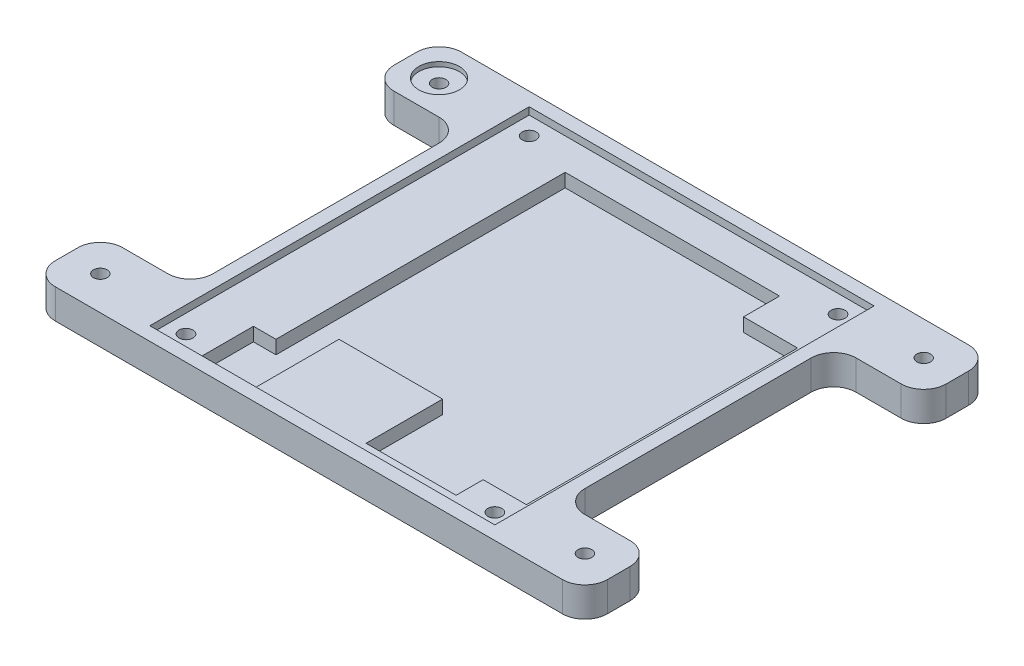
SolidWorks part; units mm, degrees
ref_plane "Front Plane" through (0, 0, 0) normal (0, 0, 1) x (1, 0, 0)
ref_plane "Top Plane" through (0, 0, 0) normal (0, 1, 0) x (1, 0, 0)
ref_plane "Right Plane" through (0, 0, 0) normal (1, 0, 0) x (0, 0, -1)
sketch "Sketch1" plane through (0, 0, 0) normal (0, 1, 0) x (1, 0, 0)
  line L0 (-36.907, 45.3779) -> (-36.907, -14.8421)
  line L1 (-44.307, -29.8421) -> (45.693, -29.8421)
  line L2 (45.693, -14.8421) -> (45.693, 45.3779)
  line L3 (45.693, 60.3779) -> (-44.307, 60.3779)
  line L4 (-44.307, 60.3779) -> (-56.907, 60.3779)
  line L5 (-56.907, 60.3779) -> (-56.907, 45.3779)
  line L6 (-56.907, 45.3779) -> (-36.907, 45.3779)
  line L7 (-44.307, -29.8421) -> (-56.907, -29.8421)
  line L8 (-56.907, -29.8421) -> (-56.907, -14.8421)
  line L9 (-56.907, -14.8421) -> (-36.907, -14.8421)
  line L10 (45.693, -29.8421) -> (65.693, -29.8421)
  line L11 (65.693, -29.8421) -> (65.693, -14.8421)
  line L12 (65.693, -14.8421) -> (45.693, -14.8421)
  line L13 (45.693, 60.3779) -> (65.693, 60.3779)
  line L14 (65.693, 60.3779) -> (65.693, 45.3779)
  line L15 (65.693, 45.3779) -> (45.693, 45.3779)
  dimension "D1" = 90.22
  dimension "D2" = 82.6
  dimension "D3" = 20
  dimension "D4" = 15
  dimension "D5" = 15
  dimension "D6" = 20
  dimension "D7" = 15
  dimension "D8" = 15
  dimension "D10" = 20
  dimension "D11" = 20
extrude "Boss-Extrude1" add sketch "Sketch1" along normal blind 6.6
sketch "Sketch2" plane through (0, 6.6, 0) normal (0, 1, 0) x (1, 0, 0)
  line L0 (-33.907, 57.3779) -> (-33.907, -26.8421)
  line L1 (-33.907, -26.8421) -> (42.693, -26.8421)
  line L2 (42.693, -26.8421) -> (42.693, 57.3779)
  line L3 (42.693, 57.3779) -> (-33.907, 57.3779)
  line L4 (-36.907, 45.3779) -> (-36.907, -14.8421) construction
  line L5 (-56.907, -29.8421) -> (65.693, -29.8421) construction
  line L6 (65.693, 60.3779) -> (-56.907, 60.3779) construction
  line L7 (45.693, -14.8421) -> (45.693, 45.3779) construction
  circle A0 centre (38.683, 53.3679) radius 1.55
  circle A1 centre (-29.897, 53.3679) radius 1.55
  circle A2 centre (-29.897, -22.8321) radius 1.55
  circle A3 centre (38.683, -22.8321) radius 1.55
  dimension "D8" = 76.6
  dimension "D1" = 3
  dimension "D2" = 3
  dimension "D3" = 84.22
  dimension "D4" = 76.2
  dimension "D5" = 4.01
  dimension "D6" = 68.58
  dimension "D7" = 4.01
  dimension "D9" = 3
  dimension "D10" = 3
  dimension "D11" = 4.01
  dimension "D12" = 4.01
  dimension "D13" = 3
extrude "Cut-Extrude9" cut sketch "Sketch2<5>" against normal blind 1.6 contours L3 L0 L1 L2
sketch "Sketch2<5>" plane through (0, 6.6, 0) normal (0, 1, 0) x (1, 0, 0) same geometry as "Sketch2"
sketch "Sketch11" plane through (0, 5, 0) normal (0, 1, 0) x (1, 0, 0)
  line L0 (-18.907, 50.3779) -> (-18.907, -13.8421)
  line L1 (-23.907, -26.8421) -> (-11.907, -26.8421)
  line L2 (-11.907, -6.8421) -> (11.093, -6.8421)
  line L3 (11.093, -6.8421) -> (11.093, -23.8421)
  line L4 (11.093, -23.8421) -> (31.093, -23.8421)
  line L5 (31.093, -23.8421) -> (31.093, -17.8421)
  line L6 (28.693, 50.3779) -> (-18.907, 50.3779)
  line L7 (-18.907, -13.8421) -> (-23.907, -13.8421)
  line L8 (-23.907, -13.8421) -> (-23.907, -26.8421)
  line L9 (-11.907, -6.8421) -> (-11.907, -26.8421)
  line L11 (31.093, -17.8421) -> (40.693, -17.8421)
  line L12 (40.693, -17.8421) -> (40.693, 42.3779)
  line L13 (40.693, 42.3779) -> (28.693, 42.3779)
  line L14 (28.693, 42.3779) -> (28.693, 50.3779)
  line L16 (-33.907, 57.3779) -> (-33.907, -26.8421) construction
  line L17 (-33.907, -26.8421) -> (42.693, -26.8421) construction
  line L18 (42.693, -26.8421) -> (42.693, 57.3779) construction
  line L19 (42.693, 57.3779) -> (-33.907, 57.3779) construction
  line L21 (-33.907, 57.3779) -> (-33.907, -26.8421) construction
  point P23 (28.693, 46.3779)
  point P29 (31.093, -20.8421)
  dimension "D1" = 15
  dimension "D2" = 20
  dimension "D3" = 65
  dimension "D4" = 3
  dimension "D5" = 9
  dimension "D6" = 2
  dimension "D7" = 14
  dimension "D8" = 7
  dimension "D9" = 13
  dimension "D10" = 10
  dimension "D11" = 22
  dimension "D12" = 45
  dimension "D13" = 15
extrude "Cut-Extrude10" cut sketch "Sketch11" against normal blind 3
extrude "Cut-Extrude3" cut sketch "Sketch2" against normal through all contours A1 | A0 | A3 | A2
sketch "Sketch4" plane through (-31.1286, 6.6, 0) normal (0, -1, 0) x (-1, 0, 0)
  line L0 (-19.1435, -1.7378) -> (-23.3424, -3.9435)
  line L1 (-3.6123, -3.9435) -> (-7.8102, -1.7378)
  line L2 (-7.8102, -6.1461) -> (-3.6123, -3.9435)
  line L3 (-23.3424, -3.9435) -> (-19.1435, -6.1461)
  line L4 (-19.1435, -7.1869) -> (-23.3424, -9.3906)
  line L5 (-3.6123, -9.3906) -> (-7.8102, -7.1869)
  line L6 (-7.8102, -11.5952) -> (-3.6123, -9.3906)
  line L7 (-23.3424, -9.3906) -> (-19.1435, -11.5952)
  line L8 (-19.1435, -12.635) -> (-23.3424, -14.8387)
  line L9 (-3.6123, -14.8387) -> (-7.8102, -12.635)
  line L10 (-7.8102, -17.0423) -> (-3.6123, -14.8387)
  line L11 (-23.3424, -14.8387) -> (-19.1435, -17.0423)
  line L12 (-7.5017, 11.7391) -> (-4.8823, 11.7391)
  line L13 (-10.0888, 5.39) -> (-10.0888, 7.6364)
  line L14 (-4.8823, 1.2873) -> (-7.5017, 1.2873)
  line L15 (-4.663, 11.5198) -> (-4.663, 1.5066)
  line L16 (-6.3249, 2.5097) -> (-6.3249, 10.5177)
  line L17 (-7.2487, 2.5097) -> (-6.3249, 2.5097)
  line L18 (-8.4041, 7.7514) -> (-8.4041, 5.2749)
  line L19 (-6.3249, 10.5177) -> (-7.2487, 10.5177)
  line L20 (-22.2342, 4.125) -> (-22.2342, 11.5198)
  line L21 (-16.8287, 11.5198) -> (-16.8287, 4.125)
  line L22 (-18.2714, 11.7391) -> (-17.048, 11.7391)
  line L23 (-18.4916, 4.127) -> (-18.4916, 11.5198)
  line L24 (-20.5713, 11.5198) -> (-20.5713, 4.127)
  line L25 (-22.0149, 11.7391) -> (-20.7905, 11.7391)
  line L26 (-14.3304, 10.4184) -> (-14.3304, 1.5066)
  line L27 (-15.903, 10.4184) -> (-14.3304, 10.4184)
  line L28 (-16.1228, 11.5198) -> (-16.1228, 10.6377)
  line L29 (-10.9808, 11.7391) -> (-15.903, 11.7391)
  line L30 (-10.7605, 10.6377) -> (-10.7605, 11.5198)
  line L31 (-12.5529, 10.4184) -> (-10.9808, 10.4184)
  line L32 (-12.5529, 1.5066) -> (-12.5529, 10.4184)
  line L33 (-14.1121, 1.2873) -> (-12.7722, 1.2873)
  spline S0 degree 3 poles (-7.8102, -1.7378) (-13.2484, -3.8532) (-13.7073, -3.8532) (-19.1435, -1.7378) knots 4 4 4 4 5 5 5 5
  spline S1 degree 3 poles (-19.1435, -6.1461) (-13.7073, -4.0318) (-13.2484, -4.0318) (-7.8102, -6.1461) knots 1 1 1 1 2 2 2 2
  spline S2 degree 3 poles (-7.8102, -7.1869) (-13.2484, -9.3013) (-13.7073, -9.3013) (-19.1435, -7.1869) knots 4 4 4 4 5 5 5 5
  spline S3 degree 3 poles (-19.1435, -11.5952) (-13.7073, -9.4799) (-13.2484, -9.4799) (-7.8102, -11.5952) knots 1 1 1 1 2 2 2 2
  spline S4 degree 3 poles (-7.8102, -12.635) (-13.2484, -14.7504) (-13.7073, -14.7504) (-19.1435, -12.635) knots 4 4 4 4 5 5 5 5
  spline S5 degree 3 poles (-19.1435, -17.0423) (-13.7073, -14.928) (-13.2484, -14.928) (-7.8102, -17.0423) knots 1 1 1 1 2 2 2 2
  spline S6 degree 3 poles (-9.5158, 11.0207) (-9.1398, 11.5079) (-8.5192, 11.7391) (-7.5017, 11.7391) knots 10 10 10 10 11 11 11 11
  spline S7 degree 3 poles (-10.0888, 7.6364) (-10.0888, 9.2824) (-10.0709, 10.3559) (-9.5158, 11.0207) knots 9 9 9 9 10 10 10 10
  spline S8 degree 3 poles (-9.5158, 2.0057) (-10.0709, 2.6705) (-10.0888, 3.744) (-10.0888, 5.39) knots 7 7 7 7 8 8 8 8
  spline S9 degree 3 poles (-7.5017, 1.2873) (-8.5192, 1.2873) (-9.1398, 1.5185) (-9.5158, 2.0057) knots 6 6 6 6 7 7 7 7
  spline S10 degree 3 poles (-4.7206, 1.3459) (-4.7558, 1.3112) (-4.8039, 1.2873) (-4.8823, 1.2873) knots 4 4 4 4 5 5 5 5
  spline S11 degree 3 poles (-4.663, 1.5066) (-4.663, 1.4282) (-4.6858, 1.3806) (-4.7206, 1.3459) knots 3 3 3 3 4 4 4 4
  spline S12 degree 3 poles (-4.7206, 11.6815) (-4.6858, 11.6458) (-4.663, 11.5992) (-4.663, 11.5198) knots 1 1 1 1 2 2 2 2
  spline S13 degree 3 poles (-4.8823, 11.7391) (-4.8039, 11.7391) (-4.7558, 11.7152) (-4.7206, 11.6815) knots 0 0 0 0 1 1 1 1
  spline S14 degree 3 poles (-8.0885, 2.8014) (-7.9, 2.5752) (-7.6565, 2.5097) (-7.2487, 2.5097) knots 5 5 5 5 6 6 6 6
  spline S15 degree 3 poles (-8.4041, 5.2749) (-8.4041, 3.8551) (-8.3793, 3.1507) (-8.0885, 2.8014) knots 4 4 4 4 5 5 5 5
  spline S16 degree 3 poles (-8.0885, 10.225) (-8.3793, 9.8757) (-8.4041, 9.1713) (-8.4041, 7.7514) knots 2 2 2 2 3 3 3 3
  spline S17 degree 3 poles (-7.2487, 10.5177) (-7.6565, 10.5177) (-7.9, 10.4512) (-8.0885, 10.225) knots 1 1 1 1 2 2 2 2
  spline S18 degree 3 poles (-21.6364, 1.9045) (-22.1156, 2.4611) (-22.2342, 3.1259) (-22.2342, 4.125) knots 20 20 20 20 21 21 21 21
  spline S19 degree 3 poles (-19.5364, 1.1554) (-20.5658, 1.1554) (-21.2286, 1.4312) (-21.6364, 1.9045) knots 19 19 19 19 20 20 20 20
  spline S20 degree 3 poles (-17.4027, 1.9035) (-17.8467, 1.4143) (-18.5189, 1.1554) (-19.5364, 1.1554) knots 18 18 18 18 19 19 19 19
  spline S21 degree 3 poles (-16.8287, 4.125) (-16.8287, 3.0485) (-16.9751, 2.3738) (-17.4027, 1.9035) knots 17 17 17 17 18 18 18 18
  spline S22 degree 3 poles (-16.8873, 11.6815) (-16.8515, 11.6458) (-16.8287, 11.5992) (-16.8287, 11.5198) knots 15 15 15 15 16 16 16 16
  spline S23 degree 3 poles (-17.048, 11.7391) (-16.9691, 11.7391) (-16.921, 11.7152) (-16.8873, 11.6815) knots 14 14 14 14 15 15 15 15
  spline S24 degree 3 poles (-18.4321, 11.6815) (-18.3984, 11.7152) (-18.3502, 11.7391) (-18.2714, 11.7391) knots 12 12 12 12 13 13 13 13
  spline S25 degree 3 poles (-18.4916, 11.5198) (-18.4916, 11.5992) (-18.4673, 11.6458) (-18.4321, 11.6815) knots 11 11 11 11 12 12 12 12
  spline S26 degree 3 poles (-18.8007, 2.6238) (-18.5636, 2.8848) (-18.4916, 3.3283) (-18.4916, 4.127) knots 9 9 9 9 10 10 10 10
  spline S27 degree 3 poles (-19.5151, 2.344) (-19.2085, 2.344) (-18.9773, 2.4294) (-18.8007, 2.6238) knots 8 8 8 8 9 9 9 9
  spline S28 degree 3 poles (-20.2627, 2.6218) (-20.0925, 2.4353) (-19.8514, 2.344) (-19.5151, 2.344) knots 7 7 7 7 8 8 8 8
  spline S29 degree 3 poles (-20.5713, 4.127) (-20.5713, 3.3561) (-20.5127, 2.8977) (-20.2627, 2.6218) knots 6 6 6 6 7 7 7 7
  spline S30 degree 3 poles (-20.6298, 11.6815) (-20.5946, 11.6458) (-20.5713, 11.5992) (-20.5713, 11.5198) knots 4 4 4 4 5 5 5 5
  spline S31 degree 3 poles (-20.7905, 11.7391) (-20.7122, 11.7391) (-20.6645, 11.7152) (-20.6298, 11.6815) knots 3 3 3 3 4 4 4 4
  spline S32 degree 3 poles (-22.1756, 11.6815) (-22.1414, 11.7152) (-22.0928, 11.7391) (-22.0149, 11.7391) knots 1 1 1 1 2 2 2 2
  spline S33 degree 3 poles (-22.2342, 11.5198) (-22.2342, 11.5992) (-22.2104, 11.6458) (-22.1756, 11.6815) knots 0 0 0 0 1 1 1 1
  spline S34 degree 3 poles (-16.0652, 10.476) (-16.03, 10.4413) (-15.9819, 10.4184) (-15.903, 10.4184) knots 17 17 17 17 18 18 18 18
  spline S35 degree 3 poles (-16.1228, 10.6377) (-16.1228, 10.5593) (-16.0985, 10.5107) (-16.0652, 10.476) knots 16 16 16 16 17 17 17 17
  spline S36 degree 3 poles (-16.0652, 11.6815) (-16.0985, 11.6458) (-16.1228, 11.5992) (-16.1228, 11.5198) knots 14 14 14 14 15 15 15 15
  spline S37 degree 3 poles (-15.903, 11.7391) (-15.9819, 11.7391) (-16.03, 11.7152) (-16.0652, 11.6815) knots 13 13 13 13 14 14 14 14
  spline S38 degree 3 poles (-10.819, 11.6815) (-10.8548, 11.7152) (-10.9019, 11.7391) (-10.9808, 11.7391) knots 11 11 11 11 12 12 12 12
  spline S39 degree 3 poles (-10.7605, 11.5198) (-10.7605, 11.5992) (-10.7843, 11.6458) (-10.819, 11.6815) knots 10 10 10 10 11 11 11 11
  spline S40 degree 3 poles (-10.819, 10.476) (-10.7843, 10.5107) (-10.7605, 10.5593) (-10.7605, 10.6377) knots 8 8 8 8 9 9 9 9
  spline S41 degree 3 poles (-10.9808, 10.4184) (-10.9019, 10.4184) (-10.8548, 10.4413) (-10.819, 10.476) knots 7 7 7 7 8 8 8 8
  spline S42 degree 3 poles (-12.6114, 1.3459) (-12.5757, 1.3806) (-12.5529, 1.4282) (-12.5529, 1.5066) knots 4 4 4 4 5 5 5 5
  spline S43 degree 3 poles (-12.7722, 1.2873) (-12.6943, 1.2873) (-12.6457, 1.3112) (-12.6114, 1.3459) knots 3 3 3 3 4 4 4 4
  spline S44 degree 3 poles (-14.2729, 1.3459) (-14.2376, 1.3112) (-14.19, 1.2873) (-14.1121, 1.2873) knots 1 1 1 1 2 2 2 2
  spline S45 degree 3 poles (-14.3304, 1.5066) (-14.3304, 1.4282) (-14.3076, 1.3806) (-14.2729, 1.3459) knots 0 0 0 0 1 1 1 1
extrude "Boss-Extrude2" [suppressed] add sketch "Sketch4" against normal blind 1.6
fillet "Fillet1" radius 5 12 edges at (-56.907, 3.3, -45.3779) (-56.907, 3.3, -60.3779) (-56.907, 3.3, 29.8421) (65.693, 3.3, -60.3779) (45.693, 3.3, -45.3779) (65.693, 3.3, -45.3779) (65.693, 3.3, 29.8421) (-56.907, 3.3, 14.8421) (65.693, 3.3, 14.8421) (45.693, 3.3, 14.8421) (-36.907, 3.3, 14.8421) (-36.907, 3.3, -45.3779)
sketch "Sketch5" plane through (0, 6.6, 0) normal (0, 1, 0) x (1, 0, 0)
  line L0 (60.693, 60.3779) -> (-51.907, 60.3779) construction
  line L1 (-56.907, 55.3779) -> (-56.907, 50.3779) construction
  line L2 (-41.907, -14.8421) -> (-51.907, -14.8421) construction
  line L3 (-56.907, -19.8421) -> (-56.907, -24.8421) construction
  line L4 (60.693, -14.8421) -> (50.693, -14.8421) construction
  line L5 (65.693, -24.8421) -> (65.693, -19.8421) construction
  line L6 (65.693, 50.3779) -> (65.693, 55.3779) construction
  circle A0 centre (-49.407, 52.8779) radius 1.525
  circle A1 centre (-49.407, 52.8779) radius 4.5
  circle A2 centre (-49.407, -22.3421) radius 1.525
  circle A3 centre (58.193, -22.3421) radius 1.525
  circle A4 centre (58.193, 52.8779) radius 1.525
  dimension "D1" = 3.05
  dimension "D4" = 9
  dimension "D7" = 3.05
  dimension "D10" = 3.05
  dimension "D13" = 3.05
  dimension "D2" = 7.5
  dimension "D3" = 7.5
  dimension "D5" = 7.5
  dimension "D6" = 7.5
  dimension "D8" = 7.5
  dimension "D9" = 7.5
  dimension "D11" = 7.5
  dimension "D12" = 7.5
extrude "Cut-Extrude4" cut sketch "Sketch5" against normal blind 10 contours A0 | A2 | A3 | A4
extrude "Cut-Extrude5" cut sketch "Sketch5<3>" against normal blind 1 contours A1
sketch "Sketch5<3>" plane through (0, 6.6, 0) normal (0, 1, 0) x (1, 0, 0) same geometry as "Sketch5"
sketch "Sketch6" plane through (0, 0, 0) normal (0, -1, 0) x (1, 0, 0)
  line L1 (-52.6108, 22.3968) -> (-51.0563, 19.5949)
  line L2 (-51.0563, 19.5949) -> (-47.8525, 19.5402)
  line L3 (-47.8525, 19.5402) -> (-46.2032, 22.2874)
  line L4 (-46.2032, 22.2874) -> (-47.7577, 25.0894)
  line L5 (-47.7577, 25.0894) -> (-50.9616, 25.1441)
  line L6 (-50.9616, 25.1441) -> (-52.6108, 22.3968)
  line L7 (58.333, 25.5433) -> (55.4907, 24.064)
  line L8 (55.4907, 24.064) -> (55.3506, 20.8628)
  line L9 (55.3506, 20.8628) -> (58.0529, 19.1409)
  line L10 (58.0529, 19.1409) -> (60.8953, 20.6202)
  line L11 (60.8953, 20.6202) -> (61.0354, 23.8215)
  line L12 (61.0354, 23.8215) -> (58.333, 25.5433)
  line L13 (60.5667, -50.7254) -> (57.5157, -49.746)
  line L14 (57.5157, -49.746) -> (55.142, -51.8984)
  line L15 (55.142, -51.8984) -> (55.8193, -55.0304)
  line L16 (55.8193, -55.0304) -> (58.8702, -56.0098)
  line L17 (58.8702, -56.0098) -> (61.2439, -53.8573)
  line L18 (61.2439, -53.8573) -> (60.5667, -50.7254)
  line L19 (-52.6111, -52.8458) -> (-51.0369, -55.6367)
  line L20 (-51.0369, -55.6367) -> (-47.8327, -55.6688)
  line L21 (-47.8327, -55.6688) -> (-46.2029, -52.91)
  line L22 (-46.2029, -52.91) -> (-47.7772, -50.1191)
  line L23 (-47.7772, -50.1191) -> (-50.9813, -50.087)
  line L24 (-50.9813, -50.087) -> (-52.6111, -52.8458)
  line L25 (-26.9565, 21.559) -> (-27.3242, 24.7422)
  line L26 (-27.3242, 24.7422) -> (-30.2648, 26.0152)
  line L27 (-30.2648, 26.0152) -> (-32.8376, 24.1052)
  line L28 (-32.8376, 24.1052) -> (-32.4698, 20.9221)
  line L29 (-32.4698, 20.9221) -> (-29.5293, 19.649)
  line L30 (-29.5293, 19.649) -> (-26.9565, 21.559)
  line L31 (41.3181, 21.009) -> (41.5794, 24.2026)
  line L32 (41.5794, 24.2026) -> (38.9443, 26.0257)
  line L33 (38.9443, 26.0257) -> (36.0479, 24.6552)
  line L34 (36.0479, 24.6552) -> (35.7866, 21.4616)
  line L35 (35.7866, 21.4616) -> (38.4217, 19.6385)
  line L36 (38.4217, 19.6385) -> (41.3181, 21.009)
  line L37 (41.4359, -55.0077) -> (41.4796, -51.8037)
  line L38 (41.4796, -51.8037) -> (38.7267, -50.1639)
  line L39 (38.7267, -50.1639) -> (35.9301, -51.728)
  line L40 (35.9301, -51.728) -> (35.8864, -54.932)
  line L41 (35.8864, -54.932) -> (38.6393, -56.5719)
  line L42 (38.6393, -56.5719) -> (41.4359, -55.0077)
  line L43 (-26.7033, -53.6279) -> (-28.0749, -50.7321)
  line L44 (-28.0749, -50.7321) -> (-31.2687, -50.472)
  line L45 (-31.2687, -50.472) -> (-33.0907, -53.1078)
  line L46 (-33.0907, -53.1078) -> (-31.7191, -56.0037)
  line L47 (-31.7191, -56.0037) -> (-28.5254, -56.2638)
  line L48 (-28.5254, -56.2638) -> (-26.7033, -53.6279)
  circle A0 centre (-49.407, 22.3421) radius 2.775 construction
  circle A1 centre (58.193, 22.3421) radius 2.775 construction
  circle A2 centre (58.193, -52.8779) radius 2.775 construction
  circle A3 centre (-49.407, -52.8779) radius 2.775 construction
  circle A4 centre (58.193, -52.8779) radius 1.525 construction
  circle A5 centre (-29.897, 22.8321) radius 2.775 construction
  circle A6 centre (38.683, 22.8321) radius 2.775 construction
  circle A7 centre (38.683, -53.3679) radius 2.775 construction
  circle A8 centre (-29.897, -53.3679) radius 2.775 construction
  point P40 (-51.7962, -51.4664)
  dimension "D1" = 5.55
  dimension "D2" = 5.55
  dimension "D3" = 5.55
  dimension "D4" = 5.55
  dimension "D5" = 5.55
  dimension "D6" = 5.55
  dimension "D7" = 5.55
  dimension "D8" = 5.55
extrude "Cut-Extrude6" cut sketch "Sketch6" against normal blind 2.4
sketch "Sketch10" plane through (0, 0, 0) normal (0, -1, 0) x (1, 0, 0)
  line L0 (20.693, -35.3779) -> (20.693, -29.8779)
  line L1 (20.693, -29.8779) -> (15.693, -29.8779)
  line L2 (15.693, -29.8779) -> (15.693, -35.3779)
  line L3 (15.693, -35.3779) -> (20.693, -35.3779)
  line L4 (-16.807, 64.8621) -> (-16.807, -60.1379) construction
  line L7 (20.693, -5.6579) -> (20.693, -0.1579)
  line L8 (20.693, -0.1579) -> (15.693, -0.1579)
  line L9 (15.693, -0.1579) -> (15.693, -5.6579)
  line L10 (15.693, -5.6579) -> (20.693, -5.6579)
  line L11 (45.693, 9.8421) -> (45.693, -40.3779) construction
  line L12 (60.693, -60.3779) -> (-51.907, -60.3779) construction
  line L13 (-51.907, 29.8421) -> (60.693, 29.8421) construction
  line L15 (-49.307, -5.6579) -> (-54.307, -5.6579)
  line L16 (-49.307, -0.1579) -> (-49.307, -5.6579)
  line L17 (-54.307, -0.1579) -> (-49.307, -0.1579)
  line L18 (-54.307, -5.6579) -> (-54.307, -0.1579)
  line L19 (-49.307, -35.3779) -> (-54.307, -35.3779)
  line L20 (-49.307, -29.8779) -> (-49.307, -35.3779)
  line L21 (-54.307, -29.8779) -> (-49.307, -29.8779)
  line L22 (-54.307, -35.3779) -> (-54.307, -29.8779)
  dimension "D1" = 5
  dimension "D2" = 5.5
  dimension "D3" = 5.5
  dimension "D4" = 25
  dimension "D5" = 25
  dimension "D6" = 5
  dimension "D7" = 25
  dimension "D8" = 30
extrude "Cut-Extrude8" [suppressed] cut sketch "Sketch10" against normal blind 5
fillet "Fillet7" [suppressed] radius 1
equation "\"1.6.00mm\"=2"
